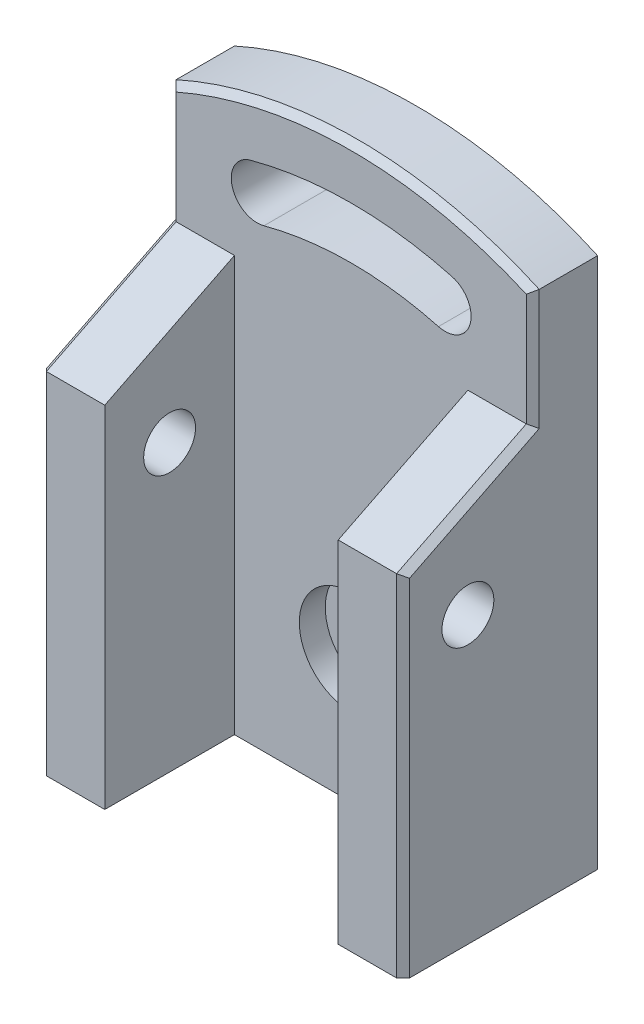
SolidWorks part; units mm, degrees
ref_plane "Front Plane" through (0, 0, 0) normal (0, 0, 1) x (1, 0, 0)
ref_plane "Top Plane" through (0, 0, 0) normal (0, 1, 0) x (1, 0, 0)
ref_plane "Right Plane" through (0, 0, 0) normal (1, 0, 0) x (0, 0, -1)
sketch "Sketch1" plane through (0, 0, 0) normal (0, 0, 1) x (1, 0, 0)
  line L0 (-63.4751, 0) -> (56.6335, 0) construction
  line L1 (0, 107.2148) -> (0, -40.6063) construction
  line L2 (-28, 0) -> (-28, 81.9677)
  line L3 (28, 81.9677) -> (28, 0)
  line L5 (0, 20) -> (-22.2819, 103.157) construction
  line L8 (0, 20) -> (22.2837, 103.1638) construction
  line L9 (-28, 0) -> (28, 0)
  circle A3 centre (0, 20) radius 8
  circle A4 centre (0, 20) radius 4
  arc A5 (-14.4939, 74.0918) -> (14.4939, 74.0918) centre (0, 20) cw construction
  arc A6 (15.5291, 77.9555) -> (-15.5291, 77.9555) centre (0, 20) ccw
  arc A7 (13.4586, 70.2281) -> (-13.4586, 70.2281) centre (0, 20) ccw
  arc A8 (13.4586, 70.2281) -> (15.5291, 77.9555) centre (14.4939, 74.0918) ccw
  arc A9 (-15.5291, 77.9555) -> (-13.4586, 70.2281) centre (-14.4939, 74.0918) ccw
  arc A10 (-28, 81.9677) -> (28, 81.9677) centre (0, 20) cw
  point P13 (0, 76)
  point P21 (4.0365, 20)
  dimension "D2" = 68
  dimension "D5" = 20
  dimension "D6" = 16
  dimension "D7" = 8
  dimension "D4" = 8
  dimension "D9" = 15
  dimension "D3" = 56
  dimension "D1" = 56
extrude "Boss-Extrude2" add sketch "Sketch1" against normal blind 10 contours A10 L2 L9 L3 A9 A6 A8 A7 A3 | A3 A4 | A4 region at (0, 41.9895, 0) region at (-7.7737, 20, 0) region at (0, 20, 0)
extrude "Cut-Extrude1" cut sketch "Sketch1<4>" against normal blind 4 contours A3
sketch "Sketch1<4>" plane through (0, 0, 0) normal (0, 0, 1) x (1, 0, 0) same geometry as "Sketch1"
extrude "Cut-Extrude2" cut sketch "Sketch1<6>" against normal blind 24 contours A4 region at (0, 20, 0)
sketch "Sketch1<6>" plane through (0, 0, 0) normal (0, 0, 1) x (1, 0, 0) same geometry as "Sketch1"
sketch "Sketch2" plane through (-28, 0, 0) normal (-1, 0, 0) x (0, 0, 1)
  line L0 (-31.9687, 0) -> (51.6999, 0) construction
  line L1 (20, 0) -> (20, 54)
  line L2 (20, 54) -> (0, 64)
  line L3 (0, 0) -> (0, 81.9677) construction
  circle A0 centre (10, 44) radius 4
  point P10 (20, 46.9043)
  line M3 (0, 0) -> (0, 81.9677)
  dimension "D3" = 8
  dimension "D1" = 44
  dimension "D2" = 64
  dimension "D4" = 30
  dimension "D5" = 10
  dimension "D6" = 10
extrude "Boss-Extrude3" add sketch "Sketch2" against normal blind 10 contours L0 L1 L2 A0 M3 region at (-28, 28.9286, 9.7049)
sketch "Sketch3" plane through (28, 0, 0) normal (1, 0, 0) x (0, 0, -1)
  line L0 (-42.1612, 0) -> (34.4628, 0) construction
  line L1 (-20, 0) -> (-20, 54) construction
  line L2 (-20, 54) -> (0, 64) construction
  line L3 (-20, 0) -> (-20, 54)
  line L4 (-20, 54) -> (0, 64)
  line L5 (-20, 0) -> (0, 0)
  circle A0 centre (-10, 44) radius 4 construction
  circle A1 centre (-10, 44) radius 4
  line M2 (0, 81.9677) -> (0, 0)
extrude "Boss-Extrude4" add sketch "Sketch3" against normal blind 10 contours L3 L5 L4 A1 M2 region at (28, 28.9286, 9.7049)
chamfer "Chamfer1" distance 1 angle 45 7 edges at (28, 27, 20) (28, 59, 10) (28, 72.9839, 0) (0, 88, 0) (-28, 72.9839, 0) (-28, 59, 10) (-28, 27, 20)
